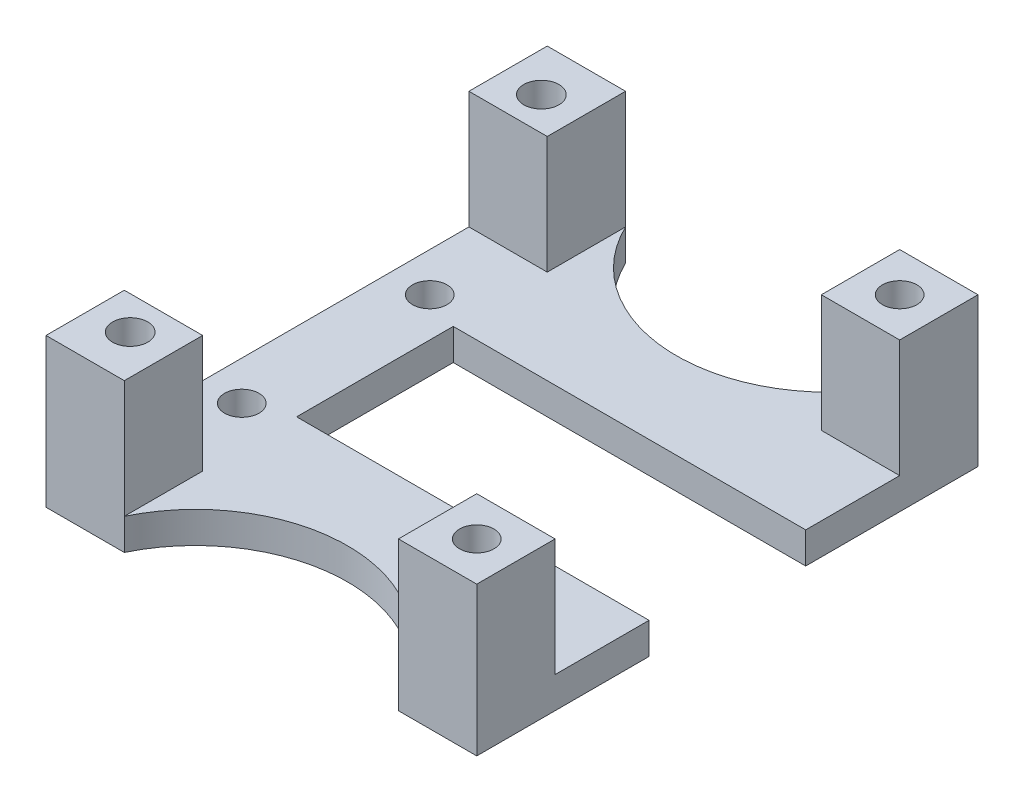
SolidWorks part; units mm, degrees
ref_plane "Front Plane" through (0, 0, 0) normal (0, 0, 1) x (1, 0, 0)
ref_plane "Top Plane" through (0, 0, 0) normal (0, 1, 0) x (1, 0, 0)
ref_plane "Right Plane" through (0, 0, 0) normal (1, 0, 0) x (0, 0, -1)
sketch "Sketch1" plane through (0, 0, 0) normal (0, 1, 0) x (1, 0, 0)
  line L0 (10, 10) -> (10, -10)
  line L1 (0, -20) -> (55, -20)
  line L2 (0, -20) -> (0, 20)
  line L3 (0, 20) -> (55, 20)
  line L4 (55, -20) -> (55, 20) construction
  line L5 (10, -10) -> (45, -10)
  line L6 (45, -10) -> (45, 10) construction
  line L7 (45, 10) -> (10, 10)
  line L8 (45, 10) -> (55, 10)
  line L11 (55, 10) -> (55, 20)
  line L13 (27.5, -20) -> (27.5, -10) construction
  line L14 (27.5, 10) -> (27.5, 20) construction
  line L16 (45, -10) -> (55, -10)
  line L17 (55, -20) -> (55, -10)
  line L18 (55, -20) -> (55, -32)
  line L19 (55, -32) -> (45, -32)
  line L20 (45, -32) -> (45, -20) construction
  line L21 (55, 20) -> (55, 32)
  line L22 (55, 32) -> (45, 32)
  line L23 (45, 32) -> (45, 20) construction
  line L24 (0, -20) -> (0, -32)
  line L25 (0, -32) -> (10, -32)
  line L26 (10, -32) -> (10, -20) construction
  line L27 (0, 20) -> (0, 32)
  line L28 (0, 32) -> (10, 32)
  line L29 (10, 32) -> (10, 20) construction
  line L30 (-55, 0) -> (55, 0) construction
  line L31 (0, 0) -> (55, 0) construction
  arc A26 (45, -32) -> (10, -32) centre (27.5, -40.4205) ccw
  arc A27 (10, 32) -> (45, 32) centre (27.5, 40.4205) ccw
  circle A28 centre (5, -12) radius 2.2
  circle A46 centre (50, 27) radius 2.2
  circle A47 centre (50, -27) radius 2.2
  circle A48 centre (5, 12) radius 2.2
  circle A49 centre (5, 26.25) radius 2.2479 construction
  circle A50 centre (5, 26.25) radius 2.2479
  circle A51 centre (5, -26.25) radius 2.2479 construction
  circle A52 centre (5, -26.25) radius 2.2479
  point P33 (27.5, 21)
  point P34 (27.5, -21)
  point P39 (0, 0)
  dimension "D18" = 4.4
  dimension "D19" = 4.4
  dimension "D4" = 4.4
  dimension "D1" = 40
  dimension "D2" = 55
  dimension "D3" = 10
  dimension "D22" = 10
  dimension "D23" = 10
  dimension "D24" = 10
  dimension "D13" = 5
  dimension "D16" = 5
  dimension "D7" = 10
  dimension "D10" = 12
  dimension "D11" = 12
  dimension "D12" = 10
  dimension "D9" = 5
  dimension "D14" = 5
  dimension "D15" = 12
  dimension "D17" = 10
  dimension "D20" = 10
  dimension "D21" = 12
  dimension "D27" = 1
  dimension "D28" = 1
  dimension "D29" = 5
  dimension "D30" = 12
extrude "Extrude-Body" add sketch "Sketch1" along normal blind 4 contours L1 L4 L3 L2 A47 A46 L7 L6 L5 L0 | L20 L19 L18 L1 A47 | L22 L23 L3 L21 A46 | L29 L28 L27 L3 | L25 L26 L1 L24 region at (9.3199, 0, 0) region at (27.5, 0, -20.5629) region at (54.4371, 0, 26)
sketch "Sketch5" plane through (0, 4, 0) normal (0, 1, 0) x (1, 0, 0)
  line L9 (45, -22) -> (55, -22)
  line L21 (55, -22) -> (55, -32)
  line L36 (55, -32) -> (45, -32)
  line L37 (45, -32) -> (45, -22)
  line L38 (55, 22) -> (55, 32)
  line L39 (55, 32) -> (45, 32)
  line L41 (45, 32) -> (45, 22)
  line L42 (45, 22) -> (55, 22)
  line L43 (10, 22) -> (10, 32)
  line L44 (10, 32) -> (0, 32)
  line L46 (0, 32) -> (0, 22)
  line L47 (0, -32) -> (0, 32) construction
  line L48 (0, 22) -> (10, 22)
  line L49 (10, -22) -> (0, -22)
  line L50 (0, -22) -> (0, -32)
  line L51 (0, -32) -> (10, -32)
  line L52 (10, -32) -> (10, -22)
  circle A0 centre (50, 27) radius 2.2
  circle A3 centre (50, -27) radius 2.2
  circle A11 centre (50, 27) radius 2.2 construction
  circle A12 centre (50, -27) radius 2.2 construction
  circle A13 centre (5, -26.25) radius 2.2479 construction
  circle A14 centre (5, -26.25) radius 2.2479
  circle A15 centre (5, 26.25) radius 2.2479 construction
  circle A16 centre (5, 26.25) radius 2.2479
  dimension "D1" = 10
  dimension "D2" = 10
  dimension "D3" = 10
  dimension "D4" = 10
  dimension "D5" = 10
  dimension "D6" = 10
  dimension "D7" = 10
  dimension "D8" = 10
extrude "Extrude-Legs" add sketch "Sketch5" along normal blind 15
sketch "Sketch6" plane through (0, 0, 0) normal (0, -1, 0) x (1, 0, 0)
  circle A0 centre (5, -26.25) radius 4.215
  circle A2 centre (5, 26.25) radius 4.215
  circle A3 centre (50, 27) radius 4.215
  circle A5 centre (50, -27) radius 4.215
  circle A6 centre (5, 26.25) radius 2.2479 construction
  circle A7 centre (5, -26.25) radius 2.2479 construction
  point P3 (0, 0)
  point P12 (0, 0)
  dimension "D1" = 8.43
  dimension "D3" = 8.43
  dimension "D4" = 8.43
  dimension "D6" = 8.43
extrude "Cut-Bolt Head Insets" cut sketch "Sketch6" against normal blind 2.5
equation "\"boltdiameter\"=4.4"
equation "\"D18@Sketch1\"=\"boltdiameter\""
equation "\"D19@Sketch1\"=\"boltdiameter\""
equation "\"boltfacediameter\"=7"
equation "\"insetNutFlat\"=8.4"
equation "\"screwInset\"=8.43"
equation "\"D1@Sketch6\"=\"screwInset\""
equation "\"D3@Sketch6\"=\"screwInset\""
equation "\"D4@Sketch6\"=\"screwInset\""
equation "\"D6@Sketch6\"=\"screwInset\""
equation "\"slotLength\"=80"
